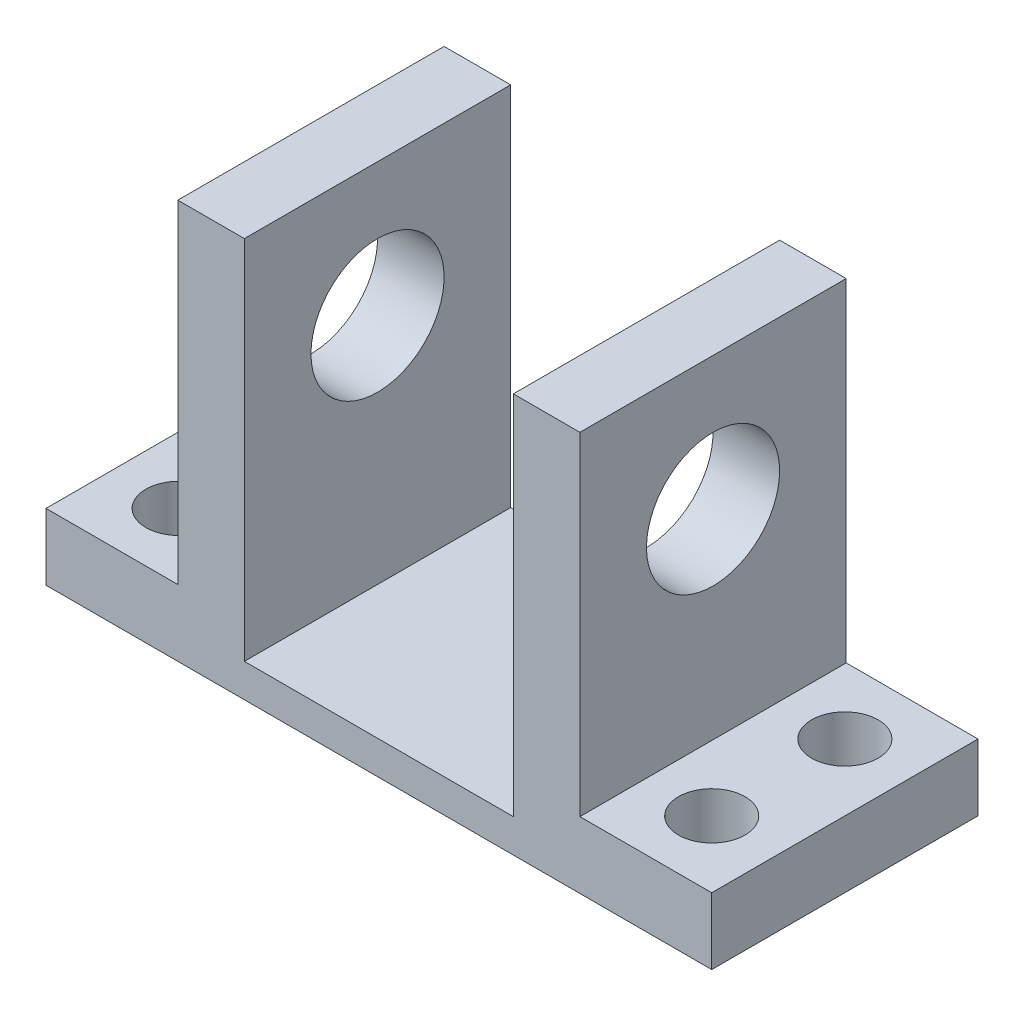
SolidWorks part; units mm, degrees
material "6061-T6 (SS)"
ref_plane "Front Plane" through (0, 0, 0) normal (0, 0, 1) x (1, 0, 0)
ref_plane "Top Plane" through (0, 0, 0) normal (0, 1, 0) x (1, 0, 0)
ref_plane "Right Plane" through (0, 0, 0) normal (1, 0, 0) x (0, 0, -1)
sketch "Sketch2" plane through (0, 0, 0) normal (0, 1, 0) x (1, 0, 0)
  line L0 (6.35, 0) -> (6.35, 25.4)
  line L1 (0, 0) -> (38.1, 0)
  line L2 (0, 0) -> (0, 25.4)
  line L3 (0, 25.4) -> (38.1, 25.4)
  line L4 (38.1, 0) -> (38.1, 25.4)
  line L5 (31.75, 0) -> (31.75, 25.4)
  dimension "D1" = 38.1
  dimension "D2" = 25.4
  dimension "D3" = 6.35
  dimension "D4" = 6.35
extrude "Boss-Extrude1" add sketch "Sketch2" along normal blind 38.1 contours L3 L2 L1 L0 | L5 L1 L4 L3 region at (3.175, 0, -12.7) region at (34.925, 0, -12.7)
extrude "Boss-Extrude2" add sketch "Sketch2<3>" along normal blind 3.175 contours L1 L5 L3 L0 region at (19.05, 0, -12.7)
sketch "Sketch2<3>" plane through (0, 0, 0) normal (0, 1, 0) x (1, 0, 0) same geometry as "Sketch2"
sketch "Sketch3" plane through (0, 0, 0) normal (-1, 0, 0) x (0, 0, 1)
  line L0 (-12.7, 38.1) -> (-12.7, 25.4) construction
  line L1 (0, 38.1) -> (-25.4, 38.1) construction
  circle A0 centre (-12.7, 25.4) radius 6.35
  dimension "D2" = 12.7
  dimension "D1" = 12.7
extrude "Cut-Extrude1" cut sketch "Sketch3" against normal through all
sketch "Sketch4" plane through (0, 0, 0) normal (-1, 0, 0) x (0, 0, 1)
  line L0 (0, 38.1) -> (0, 0) construction
  line L1 (-25.4, 0) -> (0, 0)
  line L2 (-25.4, 0) -> (-25.4, 6.35)
  line L3 (-25.4, 6.35) -> (0, 6.35)
  line L4 (0, 0) -> (0, 6.35)
  dimension "D1" = 6.35
extrude "Boss-Extrude3" add sketch "Sketch4" along normal blind 12.7
sketch "Sketch9" plane through (38.1, 0, 0) normal (1, 0, 0) x (0, 0, -1)
  line L0 (25.4, 38.1) -> (25.4, 0) construction
  line L1 (0, 0) -> (25.4, 0)
  line L2 (0, 0) -> (0, 6.35)
  line L3 (0, 6.35) -> (25.4, 6.35)
  line L4 (25.4, 0) -> (25.4, 6.35)
  dimension "D1" = 6.35
extrude "Boss-Extrude5" add sketch "Sketch9" along normal blind 12.7
sketch "Sketch10" plane through (0, 6.35, 0) normal (0, 1, 0) x (1, 0, 0)
  line L0 (-12.7, 19.05) -> (50.8, 19.05) construction
  line L1 (-12.7, 0) -> (-12.7, 25.4) construction
  line L2 (50.8, 25.4) -> (50.8, 0) construction
  line L3 (-12.7, 6.35) -> (50.8, 6.35) construction
  line L4 (-12.7, 0) -> (0, 0) construction
  line L5 (-12.7, 25.4) -> (0, 25.4) construction
  dimension "D1" = 6.35
  dimension "D2" = 6.35
hole_wizard "1/4 (0.25) Diameter Hole1" positions "3DSketch3" profile "Sketch11" hole size "1/4" standard "ANSI Inch"
sketch3d "3DSketch3"
  line L0 (-12.7, 6.35, -19.05) -> (50.8, 6.35, -19.05) construction
  line L1 (-12.7, 6.35, -6.35) -> (50.8, 6.35, -6.35) construction
  point P0 (-6.35, 6.35, -19.05)
  point P4 (-6.35, 6.35, -6.35)
  point P8 (44.45, 6.35, -6.35)
  point P10 (44.45, 6.35, -19.05)
  dimension "D1" = 6.35
  dimension "D2" = 6.35
  dimension "D3" = 6.35
  dimension "D4" = 6.35
sketch "Sketch11" plane through (-6.35, 6.35, -19.05) normal (1, 0, 0) x (0, 0, 1)
  line L0 (0, 0) -> (0, 27.3077)
  line L1 (0, 27.3077) -> (3.175, 25.4)
  line L2 (3.175, 25.4) -> (3.175, 0)
  line L5 (3.175, 0) -> (0, 0)
  line L10 (0, 27.3077) -> (-3.175, 25.4) construction
  line L11 (0, -6.35) -> (0, 107.95) construction
  dimension "Hole Dia." = 6.35
  dimension "Hole Depth" = 25.4
  dimension "Drill Angle" = 118
sketch "Sketch13" plane through (6.35, 0, 0) normal (1, 0, 0) x (0, 0, -1)
  line L1 (0, 3.175) -> (25.4, 3.175)
  line L2 (0, 3.175) -> (0, 38.1)
  line L3 (0, 38.1) -> (25.4, 38.1)
  line L4 (25.4, 3.175) -> (25.4, 38.1)
  circle A0 centre (12.7, 25.4) radius 6.35
  circle A1 centre (12.7, 25.4) radius 6.35 construction
extrude "Cut-Extrude2" cut sketch "Sketch13" against normal blind 0.127
sketch "Sketch14" plane through (31.75, 0, 0) normal (-1, 0, 0) x (0, 0, 1)
  line L1 (-25.4, 3.175) -> (0, 3.175)
  line L2 (-25.4, 3.175) -> (-25.4, 38.1)
  line L3 (-25.4, 38.1) -> (0, 38.1)
  line L4 (0, 3.175) -> (0, 38.1)
  circle A0 centre (-12.7, 25.4) radius 6.35
  circle A1 centre (-12.7, 25.4) radius 6.35 construction
extrude "Cut-Extrude3" cut sketch "Sketch14" against normal blind 0.127
sketch "Sketch15" plane through (0, 0, 0) normal (-1, 0, 0) x (0, 0, 1)
  line L1 (-25.4, 6.35) -> (0, 6.35)
  line L2 (-25.4, 6.35) -> (-25.4, 38.1)
  line L3 (-25.4, 38.1) -> (0, 38.1)
  line L4 (0, 6.35) -> (0, 38.1)
  circle A0 centre (-12.7, 25.4) radius 6.35
  circle A1 centre (-12.7, 25.4) radius 6.35 construction
sketch "Sketch16" plane through (38.1, 0, 0) normal (1, 0, 0) x (0, 0, -1)
  line L1 (0, 6.35) -> (25.4, 6.35)
  line L2 (0, 6.35) -> (0, 38.1)
  line L3 (0, 38.1) -> (25.4, 38.1)
  line L4 (25.4, 6.35) -> (25.4, 38.1)
  circle A0 centre (12.7, 25.4) radius 6.35
  circle A2 centre (12.7, 25.4) radius 6.35 construction
extrude "Boss-Extrude8" add sketch "Sketch16" along normal blind 0.127
extrude "Boss-Extrude9" add sketch "Sketch15" along normal blind 0.127
